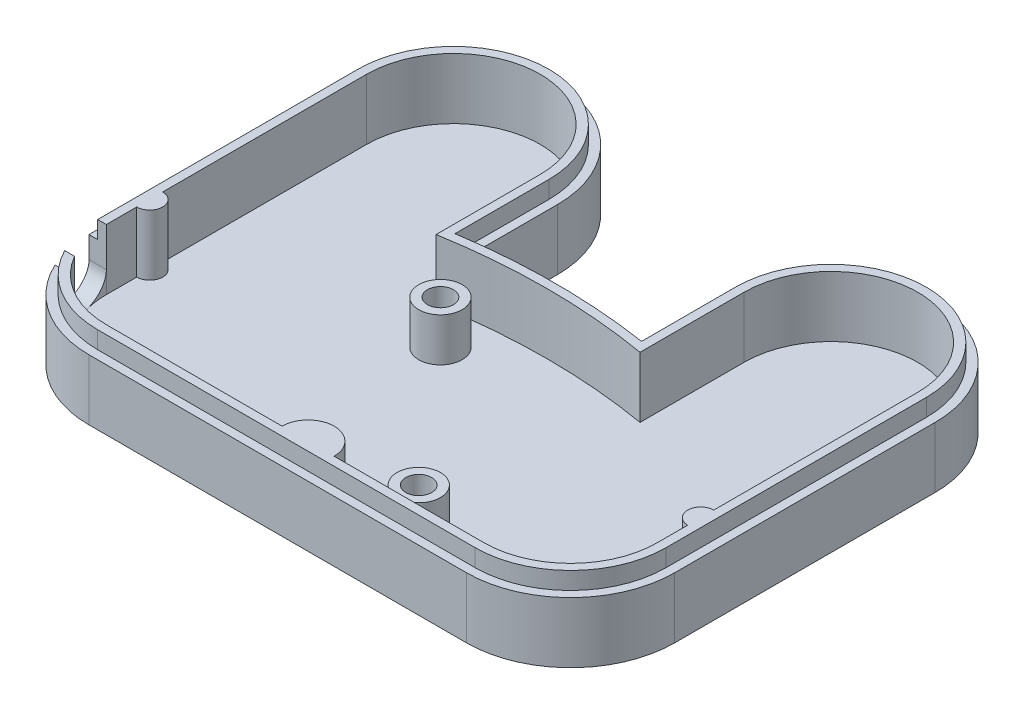
SolidWorks part; units mm, degrees
ref_plane "前视基准面" through (0, 0, 0) normal (0, 0, 1) x (1, 0, 0)
ref_plane "上视基准面" through (0, 0, 0) normal (0, 1, 0) x (1, 0, 0)
ref_plane "右视基准面" through (0, 0, 0) normal (1, 0, 0) x (0, 0, -1)
sketch "草图1" plane through (0, 0, 0) normal (0, 1, 0) x (1, 0, 0)
  line L0 (0, 28) -> (0, 40)
  line L1 (10, 0) -> (53.5, 0)
  line L2 (0, 10) -> (0, 28)
  line L3 (10, -2) -> (53.5, -2)
  line L4 (63.5, 10) -> (63.5, 28)
  line L5 (20, 28) -> (20, 40)
  line L6 (63.5, 40) -> (63.5, 28)
  line L7 (43.5, 40) -> (43.5, 28)
  line L8 (0, 40) -> (20, 40) construction
  line L9 (43.5, 40) -> (63.5, 40) construction
  line L10 (65.5, 10) -> (65.5, 28)
  line L11 (65.5, 40) -> (65.5, 28)
  line L12 (41.5, 40) -> (41.5, 30.3324)
  line L13 (22, 30.3324) -> (22, 40)
  line L14 (-2, 28) -> (-2, 40)
  line L15 (-2, 10) -> (-2, 28)
  line L16 (42.5, 40) -> (42.5, 29.176)
  line L17 (64.5, 40) -> (64.5, 28)
  line L18 (64.5, 10) -> (64.5, 28)
  line L19 (10, -1) -> (53.5, -1)
  line L20 (-1, 10) -> (-1, 28)
  line L21 (-1, 28) -> (-1, 40)
  line L22 (21, 29.176) -> (21, 40)
  arc A0 (20, 40) -> (0, 40) centre (10, 40) ccw
  arc A1 (63.5, 40) -> (43.5, 40) centre (53.5, 40) ccw
  arc A2 (53.5, 0) -> (63.5, 10) centre (53.5, 10) ccw
  arc A3 (0, 10) -> (10, 0) centre (10, 10) ccw
  arc A4 (20, 28) -> (43.5, 28) centre (31.75, -40.5313) cw
  arc A5 (53.5, -2) -> (65.5, 10) centre (53.5, 10) ccw
  arc A6 (65.5, 40) -> (41.5, 40) centre (53.5, 40) ccw
  arc A7 (22, 30.3324) -> (41.5, 30.3324) centre (31.75, -40.5313) cw
  arc A8 (22, 40) -> (-2, 40) centre (10, 40) ccw
  arc A9 (-2, 10) -> (10, -2) centre (10, 10) ccw
  arc A10 (21, 29.176) -> (42.5, 29.176) centre (31.75, -40.5313) cw
  arc A11 (64.5, 40) -> (42.5, 40) centre (53.5, 40) ccw
  arc A12 (53.5, -1) -> (64.5, 10) centre (53.5, 10) ccw
  arc A13 (-1, 10) -> (10, -1) centre (10, 10) ccw
  arc A14 (21, 40) -> (-1, 40) centre (10, 40) ccw
  point P14 (63.5, 0)
  point P15 (63.5, 0)
  point P18 (0, 0)
  point P20 (0, 0)
  dimension "D5" = 12
  dimension "D6" = 10
  dimension "D1" = 63.5
  dimension "D2" = 28
  dimension "D3" = 12
  dimension "D4" = 20
  dimension "D7" = 2
  dimension "D8" = 1
extrude "凸台-拉伸1" add sketch "草图1" along normal blind 2 contours L2 L0 A0 L5 A4 L7 A1 L6 L4 A2 L1 A3
extrude "凸台-拉伸3" add sketch "草图1<4>" along normal blind 9 contours L2 L0 A0 L5 A4 L7 A1 L6 L4 A2 L1 A3 | A13 L19 A12 L18 L17 A11 L16 A10 L22 A14 L21 L20
sketch "草图1<4>" plane through (0, 0, 0) normal (0, 1, 0) x (1, 0, 0) same geometry as "草图1"
extrude "凸台-拉伸5" add sketch "草图1<6>" along normal blind 7 contours L15 L14 A8 L13 A7 L12 A6 L11 L10 A5 L3 A9 | L20 L21 A14 L22 A10 L16 A11 L17 L18 A12 L19 A13
sketch "草图1<6>" plane through (0, 0, 0) normal (0, 1, 0) x (1, 0, 0) same geometry as "草图1"
sketch "草图3" plane through (0, 2, 0) normal (0, 1, 0) x (1, 0, 0)
  line L0 (63.5, 16.5) -> (63.5, 13.5)
  line L2 (10, 15) -> (53.5, 15)
  line L3 (0, 15) -> (63.5, 15) construction
  line L4 (63.5, 10) -> (63.5, 40) construction
  line L5 (0, 15) -> (0, 16.5)
  line L6 (0, 10) -> (0, 40) construction
  line L7 (0, 15) -> (0, 13.5)
  line L8 (42, 1.2) -> (42, 7.9771) construction
  line L9 (31.75, 0) -> (31.75, 38.4798) construction
  line L10 (10, 0) -> (53.5, 0) construction
  line L11 (30.25, 0) -> (36.25, 0)
  line L12 (10, 24) -> (53.5, 24)
  line L13 (18.6444, 24) -> (28.75, 24) construction
  line L17 (38.9854, 4) -> (45.2441, 4) construction
  arc A0 (0, 16.5) -> (0, 13.5) centre (0, 15) cw
  arc A1 (63.5, 16.5) -> (63.5, 13.5) centre (63.5, 15) ccw
  circle A3 centre (24.5, 24) radius 1.5
  circle A4 centre (24.5, 24) radius 2.5
  circle A5 centre (42, 4) radius 1.5
  circle A6 centre (42, 4) radius 2.5
  arc A7 (36.25, 0) -> (30.25, 0) centre (33.25, 0) ccw
  line M3 (10, 0) -> (53.5, 0)
  line M11 (0, 40) -> (0, 10)
  dimension "D2" = 24
  dimension "D4" = 17.5
  dimension "D6" = 8.75
  dimension "D8" = 3
  dimension "D9" = 5
  dimension "D10" = 3
  dimension "D11" = 5
  dimension "D5" = 21.5
  dimension "D7" = 20
  dimension "D3" = 24.5
  dimension "D1" = 15
extrude "凸台-拉伸8" add sketch "草图3" along normal blind 5 contours A3 | A4 | A6 | A5
extrude "凸台-拉伸9" add sketch "草图3<7>" along normal blind 7 contours A7 M3 | A0 M11 | A1 L0 region at (0.6366, 2, -15) region at (33.25, 2, -1.2732)
sketch "草图3<7>" plane through (0, 2, 0) normal (0, 1, 0) x (1, 0, 0) same geometry as "草图3"
sketch "草图4" plane through (-2, 0, 0) normal (-1, 0, 0) x (0, 0, 1)
  line L0 (-10, 4.5) -> (-10, 9)
  line L1 (-10, 9) -> (-5, 9)
  line L2 (-5, 9) -> (-5, 4.5)
  line L4 (-10, 7) -> (-10, 0) construction
  arc A0 (-10, 4.5) -> (-5, 4.5) centre (-7.5, 4.5) ccw
extrude "切除-拉伸2" cut sketch "草图4" against normal blind 5
